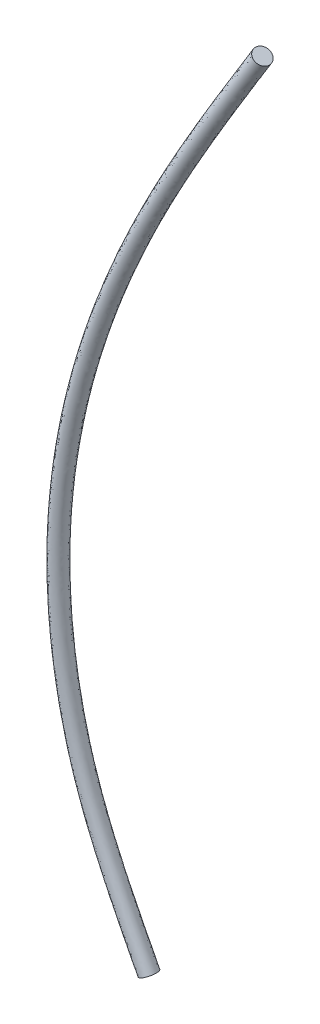
SolidWorks part; units mm, degrees
material "Acero inoxidable (ferrítico)"
ref_plane "Alzado" through (0, 0, 0) normal (0, 0, 1) x (1, 0, 0)
ref_plane "Planta" through (0, 0, 0) normal (0, 1, 0) x (1, 0, 0)
ref_plane "Vista lateral" through (0, 0, 0) normal (1, 0, 0) x (0, 0, -1)
sketch3d "Sk_Cable_principal"
  spline S0 degree 3 poles (418.3251, 430.1027, 0) (416.1668, 434.2577, 0) (410.7895, 444.6097, 0) (408.01, 465.2166, 0) (414.9496, 489.8601, 0) (424.4292, 505.2869, 0) (429.4302, 513.4254, 0) knots 0 0 0 0 0.157138 0.391504 0.678982 1 1 1 1
sweep "Cable_principal" add path "Sk_Cable_principal" circular profile diameter 1.6 parameters "D3"=1.6
